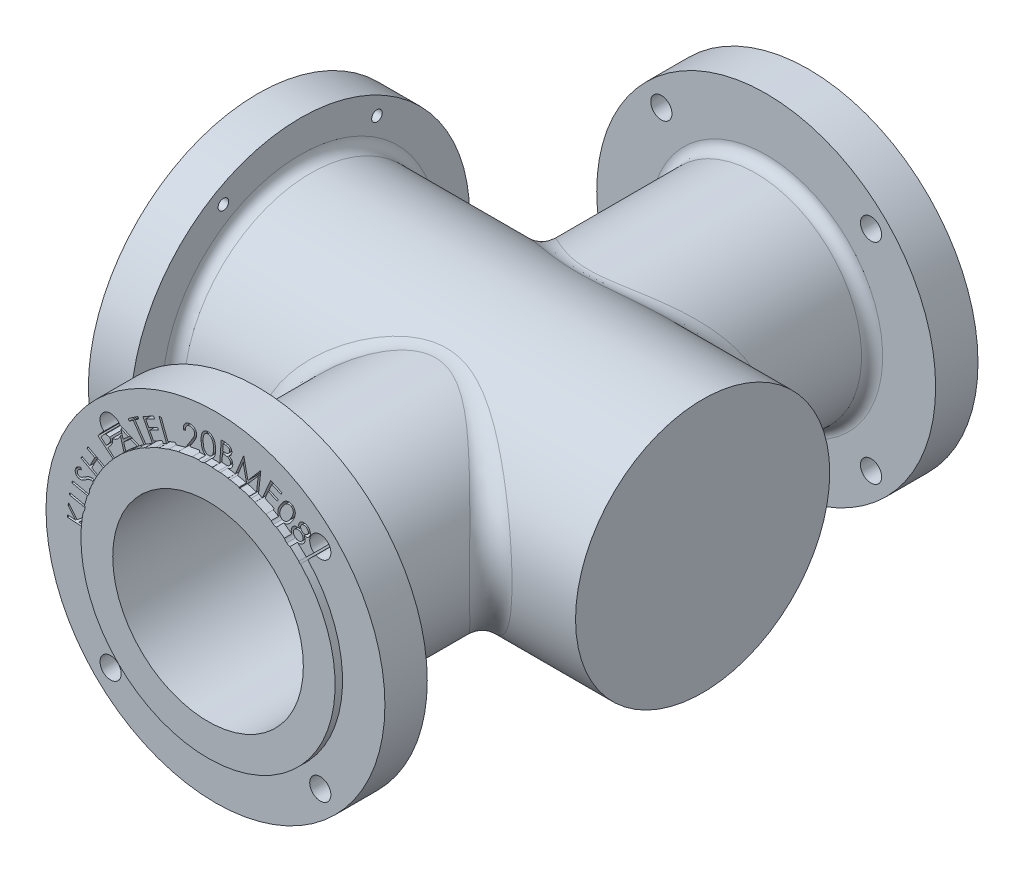
SolidWorks part; units mm, degrees
ref_plane "Front" through (0, 0, 0) normal (0, 0, 1) x (1, 0, 0)
ref_plane "Top" through (0, 0, 0) normal (0, 1, 0) x (1, 0, 0)
ref_plane "Right" through (0, 0, 0) normal (1, 0, 0) x (0, 0, -1)
sketch "Sketch1" plane through (0, 0, 0) normal (0, 1, 0) x (1, 0, 0)
  line L0 (0, 14) -> (0, -14)
  line L1 (-1024, 0) -> (-12, 0) construction
  line L2 (0, -14) -> (8, -14)
  line L3 (0, -14) -> (0, -11.5)
  line L4 (5.5, -12) -> (8, -12)
  line L5 (8, -14) -> (8, -12)
  line L6 (0, -14) -> (6, -14)
  line L7 (0, -14) -> (0, -14.35)
  line L8 (0, -14.35) -> (6, -14.35)
  line L9 (6, -14) -> (6, -14.35)
  line L10 (6, 14) -> (6, 14.35)
  line L11 (0, 14) -> (0, 14.35)
  line L12 (8, 14) -> (8, 12)
  line L13 (0, 14.35) -> (6, 14.35)
  line L14 (0, 14) -> (8, 14)
  line L15 (5.5, 12) -> (8, 12)
  line L16 (5, 11.5) -> (5, -11.5)
  line L17 (-11, 0) -> (25.7187, 0) construction
  line L18 (-11, 0) -> (-10, 0)
  line L19 (-12, 6) -> (-12, 8)
  line L20 (-12, 8) -> (-10, 8)
  line L21 (-10, 6.5) -> (-10, 8)
  line L24 (-12, 6) -> (-11, 6)
  line L25 (-11, 0) -> (-11, 6)
  line L27 (-10, 0) -> (9, 0)
  line L28 (-10, 0) -> (-10, 6)
  line L29 (-9.5, 6) -> (9, 6)
  line L30 (9, 0) -> (9, 6)
  arc A0 (5.5, -12) -> (5, -11.5) centre (5.5, -11.5) cw
  arc A1 (5.5, 12) -> (5, 11.5) centre (5.5, 11.5) ccw
  arc A2 (-9.5, 6) -> (-10, 6.5) centre (-9.5, 6.5) cw
  point P4 (0, 0)
  dimension "D7" = 0.5
  dimension "D8" = 0.5
  dimension "D16" = 0.5
  dimension "D1" = 28
  dimension "D2" = 8
  dimension "D3" = 2
  dimension "D4" = 0.35
  dimension "D5" = 6
  dimension "D6" = 5
  dimension "D9" = 2.5
  dimension "D10" = 8
  dimension "D11" = 2
  dimension "D12" = 12
  dimension "D13" = 1
  dimension "D14" = 6
  dimension "D15" = 6
  dimension "D17" = 9
revolve "Revolve1" add sketch "Sketch1" angle 360 about L0 region at (2.8174, 0, 7.4768) region at (3, 0, 14.175) region at (2.5, 0, -3) region at (3.0242, 0, -10.393) region at (3, 0, -14.175)
sketch "Sketch4" plane through (0, 0, 14.35) normal (0, 0, 1) x (1, 0, 0)
  line L0 (0, 0) -> (4.9497, 4.9497) construction
  line L1 (0, 0) -> (0, 8) construction
  circle A0 centre (0, 0) radius 4.5
  circle A1 centre (0, 0) radius 7 construction
  circle A2 centre (4.9497, 4.9497) radius 0.5
  circle A3 centre (0, 0) radius 8 construction
  circle A4 centre (4.9497, -4.9497) radius 0.5
  circle A5 centre (-4.9497, -4.9497) radius 0.5
  circle A6 centre (-4.9497, 4.9497) radius 0.5
  dimension "D1" = 9
  dimension "D2" = 14
  dimension "D3" = 1
  dimension "D4" = 45
  dimension "D5" = 4
extrude "Cut-Extrude1" cut sketch "Sketch4" against normal through all contours A6 | A2 | A4 | A5 region at (4.9497, 4.9497, 14.35) region at (-4.9497, 4.9497, 14.35)
revolve "Revolve2" add sketch "Sketch1<3>" angle 360 about L1 region at (-5.8174, 0, -3.2308) region at (7, 0, -3)
sketch "Sketch1<3>" plane through (0, 0, 0) normal (0, 1, 0) x (1, 0, 0) same geometry as "Sketch1"
sketch "Sketch5" plane through (-12, 0, 0) normal (-1, 0, 0) x (0, 0, 1)
  circle A0 centre (0, 0) radius 7.25 construction
  circle A1 centre (7.25, 0) radius 0.25
  circle A2 centre (3.625, -6.2787) radius 0.25
  circle A3 centre (-3.625, -6.2787) radius 0.25
  circle A4 centre (-7.25, 0) radius 0.25
  circle A5 centre (-3.625, 6.2787) radius 0.25
  circle A6 centre (3.625, 6.2787) radius 0.25
  dimension "D1" = 14.5
  dimension "D2" = 0.5
  dimension "D3" = 6
extrude "Cut-Extrude2" cut sketch "Sketch5" against normal up to next
sketch "Sketch6" plane through (-11, 0, 0) normal (-1, 0, 0) x (0, 0, 1)
  circle A0 centre (0, 0) radius 4.5
  dimension "D1" = 9
extrude "Cut-Extrude3" cut sketch "Sketch6" against normal blind 19
extrude "Cut-Extrude4" cut sketch "Sketch4<3>" against normal through all contours A0 region at (0, 0, 14.35)
sketch "Sketch4<3>" plane through (0, 0, 14.35) normal (0, 0, 1) x (1, 0, 0) same geometry as "Sketch4"
fillet "Fillet1" radius 1 2 edges at (4.9958, -0.2059, 5.9965) (4.9958, 0.2059, -5.9965)
sketch "Sketch8" plane through (0, 0, 14.35) normal (0, 0, 1) x (1, 0, 0)
  text T0 "KUSH PATEL 20BME081" font "Century Gothic" height 1
extrude "Cut-Extrude7" cut sketch "Sketch8" against normal blind 2
